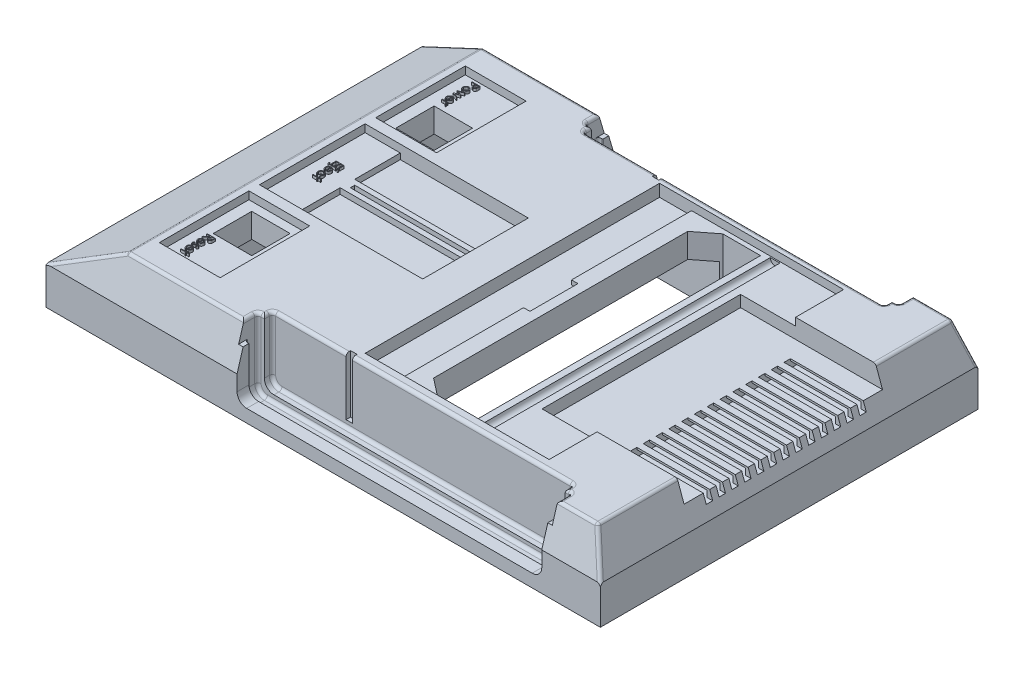
SolidWorks part; units mm, degrees
ref_plane "Front Plane" through (0, 0, 0) normal (0, 0, 1) x (1, 0, 0)
ref_plane "Top Plane" through (0, 0, 0) normal (0, 1, 0) x (1, 0, 0)
ref_plane "Right Plane" through (0, 0, 0) normal (1, 0, 0) x (0, 0, -1)
sketch "Sketch1" plane through (0, 0, 0) normal (0, 1, 0) x (1, 0, 0)
  line L1 (-219.964, -149.86) -> (0, -149.86)
  line L2 (-219.964, -149.86) -> (-219.964, 0)
  line L3 (-219.964, 0) -> (0, 0)
  line L4 (0, -149.86) -> (0, 0)
  dimension "D1" = 149.86
  dimension "D2" = 219.964
ref_plane "MiddleTop" through (0, 14.986, 0) normal (0, 1, 0) x (1, 0, 0)
sketch "Sketch2" plane through (0, 14.986, 0) normal (0, 1, 0) x (1, 0, 0)
  line L1 (0, 0) -> (-219.964, 0)
  line L2 (0, 0) -> (0, -149.86)
  line L3 (0, -149.86) -> (-219.964, -149.86)
  line L4 (-219.964, 0) -> (-219.964, -149.86)
extrude "Boss-Extrude1" add sketch "Sketch1" along normal blind 14.986
ref_plane "Plane2" through (0, 30.48, 0) normal (0, 1, 0) x (1, 0, 0)
sketch "Sketch3" plane through (0, 30.48, 0) normal (0, 1, 0) x (1, 0, 0)
  line L0 (0, -149.86) -> (-219.964, -149.86) construction
  line L1 (-192.024, -4.572) -> (-5.588, -4.572)
  line L2 (-192.024, -4.572) -> (-192.024, -145.288)
  line L3 (-192.024, -145.288) -> (-5.588, -145.288)
  line L4 (-5.588, -4.572) -> (-5.588, -145.288)
  line L5 (-219.964, 0) -> (-219.964, -149.86) construction
  line L6 (0, 0) -> (0, -149.86) construction
  dimension "D1" = 140.716
  dimension "D2" = 4.572
  dimension "D3" = 27.94
  dimension "D4" = 5.588
loft "Loft1" add profiles "Sketch2", "Sketch3" connector at (-219.964, 14.986, 149.86) connector at (-192.024, 30.48, 145.288)
sketch "Sketch4" plane through (0, 30.48, 0) normal (0, 1, 0) x (1, 0, 0)
  line L0 (-192.024, -145.288) -> (-5.588, -145.288) construction
  line L1 (-189.23, -135.636) -> (-165.1, -135.636)
  line L2 (-189.23, -135.636) -> (-189.23, -100.076)
  line L3 (-189.23, -100.076) -> (-165.1, -100.076)
  line L4 (-165.1, -135.636) -> (-165.1, -100.076)
  line L5 (-192.024, -4.572) -> (-192.024, -145.288) construction
  line L6 (-5.588, -4.572) -> (-192.024, -4.572) construction
  line L7 (-189.23, -49.784) -> (-165.1, -49.784)
  line L8 (-189.23, -49.784) -> (-189.23, -14.224)
  line L9 (-189.23, -14.224) -> (-165.1, -14.224)
  line L10 (-165.1, -49.784) -> (-165.1, -14.224)
  point P12 (-177.165, -14.224)
  dimension "D1" = 35.56
  dimension "D2" = 24.13
  dimension "D3" = 9.652
  dimension "D4" = 2.794
  dimension "D5" = 24.13
  dimension "D6" = 35.56
  dimension "D7" = 2.794
  dimension "D8" = 9.652
sketch "Sketch5" plane through (0, 30.48, 0) normal (0, 1, 0) x (1, 0, 0)
  line L0 (-189.23, -100.076) -> (-165.1, -100.076) construction
  line L1 (-189.23, -95.885) -> (-124.46, -95.885)
  line L2 (-189.23, -95.885) -> (-189.23, -53.975)
  line L3 (-189.23, -53.975) -> (-124.46, -53.975)
  line L4 (-124.46, -95.885) -> (-124.46, -53.975)
  line L5 (-192.024, -4.572) -> (-192.024, -145.288) construction
  dimension "D1" = 41.91
  dimension "D2" = 4.191
  dimension "D3" = 2.794
  dimension "D4" = 64.77
extrude "Cut-Extrude1" cut sketch "Sketch4" against normal blind 3.048
extrude "Cut-Extrude2" cut sketch "Sketch5" against normal blind 3.048
ref_plane "Plane3" through (0, 25.146, 0) normal (0, 1, 0) x (1, 0, 0)
sketch "Sketch6" plane through (0, 25.146, 0) normal (0, 1, 0) x (1, 0, 0)
  line L0 (-189.23, -53.975) -> (-189.23, -95.885) construction
  line L1 (-175.26, -72.0598) -> (-124.46, -72.0598)
  line L2 (-175.26, -72.0598) -> (-175.26, -77.851)
  line L3 (-175.26, -77.851) -> (-124.46, -77.851)
  line L4 (-124.46, -72.0598) -> (-124.46, -77.851)
  line L5 (-189.23, -95.885) -> (-124.46, -95.885) construction
  dimension "D1" = 50.8
  dimension "D2" = 13.97
  dimension "D3" = 5.7912
  dimension "D4" = 18.034
sketch "Sketch10" plane through (0, 30.48, 0) normal (0, 1, 0) x (1, 0, 0)
  line L6 (-219.964, -149.86) -> (0, -149.86) construction
  line L9 (-144.145, -145.1356) -> (-145.923, -145.1356)
  line L10 (-145.923, -145.1356) -> (-145.923, -139.8016)
  line L11 (-145.923, -139.8016) -> (-143.383, -139.8016)
  line L12 (-143.383, -139.8016) -> (-143.383, -136.5758)
  line L13 (-143.383, -136.5758) -> (-24.003, -136.5758)
  line L14 (-24.003, -136.5758) -> (-24.003, -139.8016)
  line L15 (-24.003, -139.8016) -> (-21.463, -139.8016)
  line L16 (-21.463, -139.8016) -> (-21.463, -145.1356)
  line L17 (-21.463, -145.1356) -> (-23.241, -145.1356)
  line L21 (-23.241, -149.86) -> (-144.145, -149.86)
  line L22 (-144.145, -145.1356) -> (-144.145, -149.86)
  line L23 (-23.241, -145.1356) -> (-23.241, -149.86)
  line L24 (0, -149.86) -> (0, 0) construction
  line L25 (-219.964, -74.93) -> (-5.588, -74.93) construction
  line L27 (-219.964, 0) -> (-219.964, -149.86) construction
  line L28 (-5.588, -145.288) -> (-5.588, -4.572) construction
  line L29 (-21.463, -4.7244) -> (-23.241, -4.7244)
  line L30 (-21.463, -10.0584) -> (-21.463, -4.7244)
  line L31 (-24.003, -10.0584) -> (-21.463, -10.0584)
  line L32 (-24.003, -13.2842) -> (-24.003, -10.0584)
  line L33 (-143.383, -13.2842) -> (-24.003, -13.2842)
  line L34 (-143.383, -10.0584) -> (-143.383, -13.2842)
  line L35 (-145.923, -10.0584) -> (-143.383, -10.0584)
  line L36 (-145.923, -4.7244) -> (-145.923, -10.0584)
  line L37 (-144.145, -4.7244) -> (-145.923, -4.7244)
  line L38 (-144.145, -4.7244) -> (-144.145, 0)
  line L39 (-23.241, 0) -> (-144.145, 0)
  line L40 (-23.241, -4.7244) -> (-23.241, 0)
  dimension "D1" = 13.2842
  dimension "D2" = 5.334
  dimension "D3" = 3.2258
  dimension "D4" = 2.54
  dimension "D5" = 124.46
  dimension "D6" = 3.2258
  dimension "D7" = 2.54
  dimension "D8" = 1.778
  dimension "D9" = 5.334
  dimension "D10" = 21.463
  dimension "D11" = 1.778
sketch "Sketch12" plane through (0, 30.48, 0) normal (0, 1, 0) x (1, 0, 0)
  line L1 (-145.923, -10.0584) -> (-21.463, -10.0584)
  line L2 (-145.923, -10.0584) -> (-145.923, -4.7244)
  line L3 (-145.923, -4.7244) -> (-21.463, -4.7244)
  line L4 (-21.463, -10.0584) -> (-21.463, -4.7244)
  line L5 (-145.923, -145.1356) -> (-21.463, -145.1356)
  line L6 (-145.923, -145.1356) -> (-145.923, -139.8016)
  line L7 (-145.923, -139.8016) -> (-21.463, -139.8016)
  line L8 (-21.463, -145.1356) -> (-21.463, -139.8016)
extrude "Cut-Extrude4" cut sketch "Sketch12" against normal blind 27.94
extrude "Cut-Extrude5" cut sketch "Sketch10" against normal blind 25.4
sketch "Sketch14" plane through (0, 30.48, 0) normal (0, 1, 0) x (1, 0, 0)
  line L1 (-145.923, -145.1356) -> (-144.145, -145.1356)
  line L2 (-145.923, -145.1356) -> (-145.923, -149.86)
  line L3 (-145.923, -149.86) -> (-144.145, -149.86)
  line L4 (-144.145, -145.1356) -> (-144.145, -149.86)
  line L5 (-21.463, -145.1356) -> (-23.241, -145.1356)
  line L6 (-21.463, -145.1356) -> (-21.463, -149.86)
  line L7 (-21.463, -149.86) -> (-23.241, -149.86)
  line L8 (-23.241, -145.1356) -> (-23.241, -149.86)
  line L9 (-145.923, -4.7244) -> (-144.145, -4.7244)
  line L10 (-145.923, -4.7244) -> (-145.923, 0)
  line L11 (-145.923, 0) -> (-144.145, 0)
  line L12 (-144.145, -4.7244) -> (-144.145, 0)
  line L13 (-21.463, -4.7244) -> (-23.241, -4.7244)
  line L14 (-21.463, -4.7244) -> (-21.463, 0)
  line L15 (-21.463, 0) -> (-23.241, 0)
  line L16 (-23.241, -4.7244) -> (-23.241, 0)
extrude "Cut-Extrude6" cut sketch "Sketch14" against normal blind 7.366
sketch "Sketch15" plane through (0, 30.48, 0) normal (0, 1, 0) x (1, 0, 0)
  line L0 (-5.588, -145.288) -> (-5.588, -4.572) construction
  line L1 (-110.363, -16.002) -> (-37.338, -16.002)
  line L2 (-110.363, -16.002) -> (-110.363, -132.842)
  line L3 (-110.363, -132.842) -> (-37.338, -132.842)
  line L4 (-37.338, -16.002) -> (-37.338, -35.052)
  line L5 (-5.588, -4.572) -> (-21.463, -4.572) construction
  line L6 (-37.338, -35.052) -> (-59.182, -35.052)
  line L7 (-59.182, -35.052) -> (-59.182, -113.792)
  line L8 (-59.182, -113.792) -> (-37.338, -113.792)
  line L9 (-37.338, -113.792) -> (-37.338, -132.842)
  dimension "D1" = 73.025
  dimension "D2" = 31.75
  dimension "D3" = 116.84
  dimension "D4" = 11.43
  dimension "D5" = 21.844
  dimension "D6" = 78.74
  dimension "D7" = 19.05
extrude "Cut-Extrude7" cut sketch "Sketch15" against normal blind 3.048
sketch "Sketch16" plane through (0, 30.48, 0) normal (0, 1, 0) x (1, 0, 0)
  line L1 (-59.182, -35.052) -> (0.508, -35.052)
  line L2 (-59.182, -35.052) -> (-59.182, -113.792)
  line L3 (-59.182, -113.792) -> (0.508, -113.792)
  line L4 (0.508, -35.052) -> (0.508, -113.792)
  dimension "D1" = 59.69
extrude "Cut-Extrude8" cut sketch "Sketch16" against normal blind 7.62
sketch "Sketch17" plane through (0, 30.48, 0) normal (0, 1, 0) x (1, 0, 0)
  line L0 (-110.363, -132.842) -> (-37.338, -132.842) construction
  line L1 (-110.363, -16.002) -> (-97.663, -16.002)
  line L2 (-110.363, -16.002) -> (-110.363, -132.842)
  line L3 (-110.363, -132.842) -> (-97.663, -132.842)
  line L4 (-97.663, -16.002) -> (-97.663, -63.627)
  line L5 (-97.663, -63.627) -> (-95.123, -63.627)
  line L6 (-95.123, -63.627) -> (-95.123, -82.677)
  line L7 (-95.123, -82.677) -> (-97.663, -82.677)
  line L8 (-97.663, -82.677) -> (-97.663, -132.842)
  dimension "D1" = 12.7
  dimension "D2" = 19.05
  dimension "D3" = 47.625
  dimension "D4" = 2.54
extrude "Cut-Extrude9" cut sketch "Sketch17" against normal blind 4.826
sketch "Sketch18" plane through (0, 30.48, 0) normal (0, 1, 0) x (1, 0, 0)
  line L0 (-83.5048, -17.78) -> (-91.313, -23.876)
  line L1 (-83.5048, -17.78) -> (-68.5188, -17.78)
  line L2 (-91.313, -23.876) -> (-91.313, -124.714)
  line L3 (-83.5048, -130.81) -> (-68.5188, -130.81)
  line L4 (-68.5188, -17.78) -> (-68.5188, -130.81)
  line L5 (-83.5048, -130.81) -> (-91.313, -124.714)
  line L6 (-97.663, -132.842) -> (-37.338, -132.842) construction
  line L8 (-95.123, -82.677) -> (-95.123, -63.627) construction
  dimension "D1" = 14.986
  dimension "D2" = 9.906
  dimension "D3" = 9.906
  dimension "D4" = 14.986
  dimension "D5" = 100.838
  dimension "D6" = 113.03
  dimension "D7" = 2.032
  dimension "D8" = 3.81
extrude "Cut-Extrude10" cut sketch "Sketch18" against normal through all
sketch "Sketch19" plane through (0, 30.48, 0) normal (0, 1, 0) x (1, 0, 0)
  line L0 (0, -149.86) -> (0, 0) construction
  line L1 (-31.75, -42.672) -> (0, -42.672)
  line L2 (-31.75, -42.672) -> (-31.75, -45.212)
  line L3 (-31.75, -45.212) -> (0, -45.212)
  line L4 (0, -42.672) -> (0, -45.212)
  line L5 (-2.8398, -35.052) -> (-59.182, -35.052) construction
  dimension "D1" = 2.54
  dimension "D2" = 31.75
  dimension "D3" = 7.62
extrude "Cut-Extrude11" cut sketch "Sketch19" against normal blind 10.922
pattern_linear "LPattern1" count 13 spacing 5.08 along (0, 0, 1) of "Cut-Extrude11"
ref_plane "Plane5" through (0, 0, 103.632) normal (0, 0, 1) x (1, 0, 0)
sketch "Sketch20" plane through (0, 0, 103.632) normal (0, 0, 1) x (1, 0, 0)
  line L0 (-2.8398, 22.86) -> (-31.75, 22.86) construction
  line L1 (-31.75, 22.098) -> (-3.81, 22.098)
  line L2 (-31.75, 22.098) -> (-31.75, 19.558)
  line L3 (-31.75, 19.558) -> (-3.81, 19.558)
  line L4 (-3.81, 22.098) -> (-3.81, 19.558)
  line L6 (-31.75, 19.558) -> (-31.75, 22.86) construction
  dimension "D1" = 0.762
  dimension "D2" = 2.54
  dimension "D3" = 0
  dimension "D4" = 27.94
extrude "Cut-Extrude12" cut sketch "Sketch20" against normal blind 63.5
sketch "Sketch25" plane through (0, 30.48, 0) normal (0, 1, 0) x (1, 0, 0)
  line L1 (-175.26, -72.0598) -> (-124.46, -72.0598)
  line L2 (-175.26, -72.0598) -> (-175.26, -53.975)
  line L3 (-175.26, -53.975) -> (-124.46, -53.975)
  line L4 (-124.46, -72.0598) -> (-124.46, -53.975)
  line L5 (-175.26, -77.851) -> (-124.46, -77.851)
  line L6 (-175.26, -77.851) -> (-175.26, -95.885)
  line L7 (-175.26, -95.885) -> (-124.46, -95.885)
  line L8 (-124.46, -77.851) -> (-124.46, -95.885)
extrude "Cut-Extrude14" cut sketch "Sketch25" against normal blind 5.334
sketch "Sketch21" plane through (0, 30.48, 0) normal (0, 1, 0) x (1, 0, 0)
  line L1 (-173.228, -74.0918) -> (-126.238, -74.0918)
  line L2 (-173.228, -74.0918) -> (-173.228, -75.819)
  line L3 (-173.228, -75.819) -> (-126.238, -75.819)
  line L4 (-126.238, -74.0918) -> (-126.238, -75.819)
  line L7 (-124.46, -53.975) -> (-189.23, -53.975) construction
  line L8 (-175.26, -95.885) -> (-124.46, -95.885) construction
  line L9 (-124.46, -95.885) -> (-124.46, -53.975) construction
  dimension "D1" = 20.1168
  dimension "D2" = 20.066
  dimension "D3" = 46.99
  dimension "D4" = 1.778
extrude "Cut-Extrude13" cut sketch "Sketch21" against normal through all
ref_plane "Plane6" through (0, 0, 16.51) normal (0, 0, 1) x (1, 0, 0)
sketch "Sketch26" plane through (0, 0, 16.51) normal (0, 0, 1) x (1, 0, 0)
  line L2 (-37.338, 27.432) -> (-97.663, 27.432) construction
  circle A0 centre (-64.008, 27.432) radius 1.905
  dimension "D3" = 3.81
  dimension "D1" = 0
  dimension "D2" = 58.42
extrude "Cut-Extrude15" cut sketch "Sketch26" along normal blind 115.57
fillet "Fillet1" radius 3.81 12 edges at (-144.145, 5.08, 2.3622) (-23.241, 5.08, 2.3622) (-144.145, 5.08, 147.4978) (-23.241, 5.08, 147.4978) (-24.003, 5.08, 138.1887) (-143.383, 5.08, 138.1887) (-143.383, 5.08, 11.6713) (-24.003, 5.08, 11.6713) (-21.463, 2.54, 142.4686) (-145.923, 2.54, 142.4686) (-145.923, 2.54, 7.3914) (-21.463, 2.54, 7.3914)
fillet "Fillet2" radius 1.27 30 edges at (-145.923, 14.732, 4.7244) (-144.8071, 3.6559, 4.7244) (-83.693, 2.54, 4.7244) (-22.5789, 3.6559, 4.7244) (-21.463, 18.415, 10.0584) (-145.923, 18.415, 10.0584) (-144.8071, 3.6559, 10.0584) (-83.693, 2.54, 10.0584) (-24.003, 19.685, 13.2842) (-143.383, 19.685, 13.2842) (-142.2671, 6.1959, 13.2842) (-83.693, 5.08, 13.2842) (-24.003, 19.685, 136.5758) (-25.1189, 6.1959, 136.5758) (-143.383, 19.685, 136.5758) (-142.2671, 6.1959, 136.5758) (-21.463, 18.415, 139.8016) (-22.5789, 3.6559, 139.8016) (-83.693, 2.54, 139.8016) (-144.8071, 3.6559, 139.8016) (-21.463, 14.732, 145.1356) (-22.5789, 3.6559, 145.1356) (-83.693, 2.54, 145.1356) (-144.8071, 3.6559, 145.1356) (-21.463, 14.732, 4.7244) (-22.5789, 3.6559, 10.0584) (-25.1189, 6.1959, 13.2842) (-83.693, 5.08, 136.5758) (-145.923, 18.415, 139.8016) (-145.923, 14.732, 145.1356)
fillet "Fillet3" radius 1.27 33 edges at (-23.368, 30.48, 139.8016) (-21.835, 30.48, 140.1736) (-23.368, 30.48, 10.0584) (-21.835, 30.48, 9.6864) (-144.018, 30.48, 10.0584) (-145.551, 30.48, 9.6864) (-144.018, 30.48, 139.8016) (-145.551, 30.48, 140.1736) (-143.383, 30.48, 11.0363) (-143.011, 30.48, 12.9122) (-24.003, 30.48, 11.0363) (-24.375, 30.48, 12.9122) (-24.003, 30.48, 138.8237) (-24.375, 30.48, 136.9478) (-143.383, 30.48, 138.8237) (-143.011, 30.48, 136.9478) (-83.693, 30.48, 13.2842) (-83.693, 30.48, 136.5758)
sketch "Sketch27" plane through (0, 30.48, 0) normal (0, 1, 0) x (1, 0, 0)
  line L0 (-139.573, -136.5758) -> (-27.813, -136.5758) construction
  line L1 (-114.173, -134.7978) -> (-111.633, -134.7978)
  line L2 (-114.173, -134.7978) -> (-114.173, -136.5758)
  line L3 (-114.173, -136.5758) -> (-111.633, -136.5758)
  line L4 (-111.633, -134.7978) -> (-111.633, -136.5758)
  line L5 (-145.923, -143.8656) -> (-145.923, -141.0716) construction
  line L6 (0, -74.93) -> (-226.7454, -74.93) construction
  line L8 (0, -148.663) -> (0, -1.197) construction
  dimension "D1" = 1.778
  dimension "D2" = 2.54
  dimension "D3" = 31.75
sketch "Sketch28" plane through (0, 30.48, 0) normal (0, 1, 0) x (1, 0, 0)
  line L2 (-114.173, -13.2842) -> (-114.173, -15.0622)
  line L3 (-114.173, -15.0622) -> (-111.633, -15.0622)
  line L4 (-111.633, -13.2842) -> (-111.633, -15.0622)
  line L5 (-145.923, -4.1972) -> (-145.923, -8.7884) construction
  line L8 (-114.173, -13.2842) -> (-111.633, -13.2842)
  line L9 (-142.113, -13.2842) -> (-25.273, -13.2842) construction
  dimension "D1" = 1.778
  dimension "D2" = 2.54
  dimension "D3" = 31.75
  dimension "D4" = 0
extrude "Cut-Extrude16" cut sketch "Sketch27" against normal blind 22.86
extrude "Cut-Extrude17" cut sketch "Sketch28" against normal blind 22.86
sketch "Sketch29" plane through (0, 0, 0) normal (0, 1, 0) x (1, 0, 0)
  line L0 (-191.6954, -5.5214) -> (-191.6954, -144.3386) construction
  line L1 (-190.4254, -18.3642) -> (-7.5454, -18.3642)
  line L2 (-190.4254, -18.3642) -> (-190.4254, -132.6642)
  line L3 (-190.4254, -132.6642) -> (-7.5454, -132.6642)
  line L4 (-7.5454, -18.3642) -> (-7.5454, -132.6642)
  line L5 (-25.273, -14.5542) -> (-111.633, -14.5542) construction
  dimension "D1" = 114.3
  dimension "D2" = 182.88
  dimension "D3" = 1.27
  dimension "D4" = 3.81
extrude "Cut-Extrude18" cut sketch "Sketch29" along normal blind 17.78
sketch "Sketch30" plane through (0, 30.48, 0) normal (0, 1, 0) x (1, 0, 0)
  line L1 (-184.6913, -46.355) -> (-169.4513, -46.355)
  line L2 (-184.6913, -46.355) -> (-184.6913, -31.115)
  line L3 (-184.6913, -31.115) -> (-169.4513, -31.115)
  line L4 (-169.4513, -46.355) -> (-169.4513, -31.115)
  line L5 (-124.46, -53.975) -> (-189.23, -53.975) construction
  line L6 (-192.3113, -144.3386) -> (-192.3113, -5.5214) construction
  line L7 (0, -74.93) -> (-237.3505, -74.93) construction
  line L8 (0, -148.663) -> (0, -1.197) construction
  line L9 (-184.6913, -118.745) -> (-169.4513, -118.745)
  line L10 (-169.4513, -103.505) -> (-169.4513, -118.745)
  line L11 (-184.6913, -103.505) -> (-169.4513, -103.505)
  line L12 (-184.6913, -103.505) -> (-184.6913, -118.745)
  dimension "D1" = 15.24
  dimension "D2" = 15.24
  dimension "D3" = 7.62
  dimension "D4" = 7.62
extrude "Cut-Extrude19" cut sketch "Sketch30" against normal through all
ref_plane "Plane7" through (0, 27.432, 0) normal (0, 1, 0) x (1, 0, 0)
sketch "Sketch31" plane through (0, 27.432, 0) normal (0, 1, 0) x (1, 0, 0)
  line L0 (-184.4444, -29.1684) -> (-184.4444, -14.224) construction
  line L1 (-165.1, -14.224) -> (-189.23, -14.224) construction
  line L2 (-184.7529, -120.6295) -> (-184.7529, -133.3206) construction
  line L3 (-184.2212, -70.0663) -> (-184.2212, -81.9385) construction
  text T0 "Power"
  text T1 "Reset"
  text T2 "Eject"
  point P6 (-184.6913, -67.0543)
  point P7 (-184.6361, -81.9385)
  point P8 (0, 0)
  point P17 (-184.2212, -70.0663)
extrude "Boss-Extrude2" add sketch "Sketch31" along normal blind 1.016
